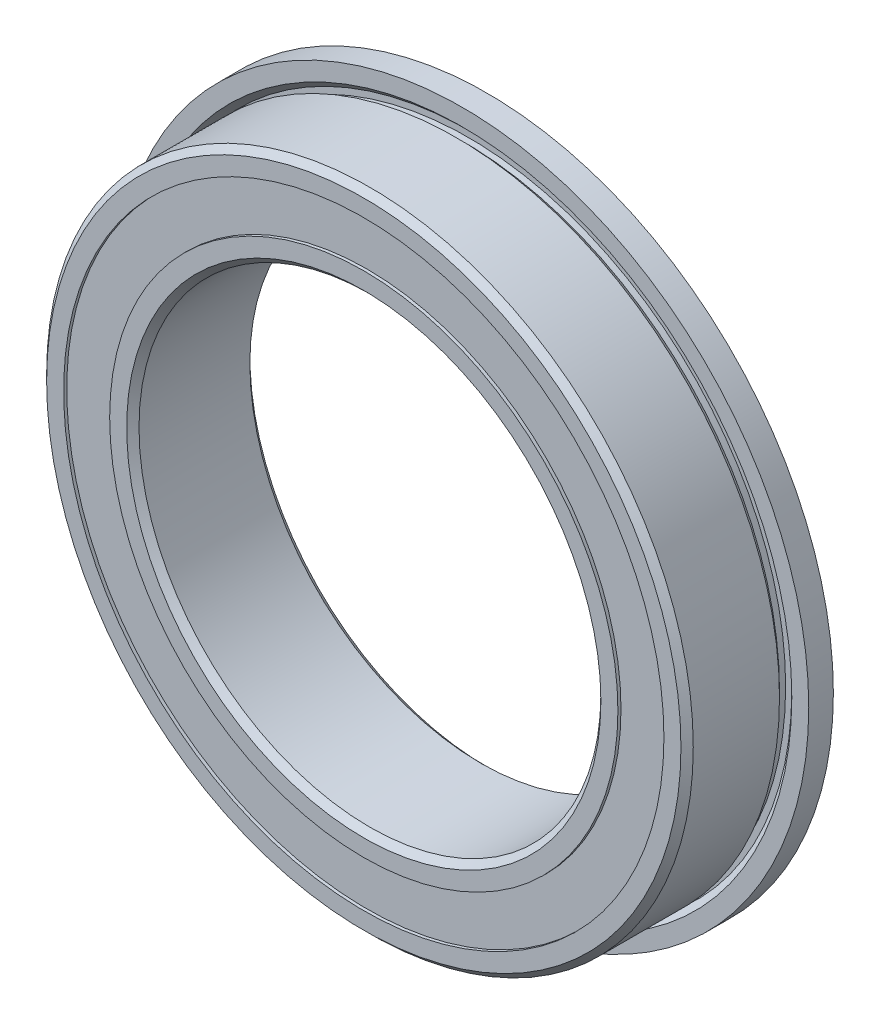
SolidWorks part; units mm, degrees
ref_plane "Front Plane" through (0, 0, 0) normal (0, 0, 1) x (1, 0, 0)
ref_plane "Top Plane" through (0, 0, 0) normal (0, 1, 0) x (1, 0, 0)
ref_plane "Right Plane" through (0, 0, 0) normal (1, 0, 0) x (0, 0, -1)
sketch "Sketch1" plane through (0, 0, 0) normal (0, 0, 1) x (1, 0, 0)
  circle A0 centre (0, 0) radius 7.5
  dimension "ID" = 15
sketch "Sketch2" plane through (0, 0, 0) normal (1, 0, 0) x (0, 0, -1)
  line L0 (-2, 0) -> (2, 0) construction
  line L1 (0, 10.5) -> (0, -10.5) construction
  line L2 (1.8, 10.5) -> (-1.8, 10.5) construction
  line L3 (-1.8, 10.5) -> (-2, 10.3)
  line L4 (-2, 10.3) -> (-2, 9.7473)
  line L5 (-2, 9.7473) -> (-0.8889, 9.7473)
  line L6 (2, 9.7473) -> (0.8889, 9.7473)
  line L7 (2, 10.3) -> (2, 9.7473)
  line L8 (1.8, 10.5) -> (2, 10.3) construction
  line L9 (0, 10.5) -> (0, 9) construction
  line L10 (0, 9) -> (0, 7.5) construction
  line L11 (1.2, 0) -> (1.2, 10.5) construction
  line L12 (2, 10.3) -> (2, 11.25)
  line L13 (2, 11.25) -> (1.2, 11.25)
  line L14 (1.2, 11.25) -> (1.2, 10.7)
  line L15 (1.2, 10.7) -> (1.4, 10.5)
  line L16 (1.4, 10.5) -> (1.4, 10.3)
  line L17 (1.4, 10.3) -> (1.2, 10.3)
  line L18 (1.2, 10.3) -> (1, 10.5)
  line L19 (-1.8, 10.5) -> (1, 10.5)
  line L20 (2, 11.25) -> (2, -11.25) construction
  line L21 (1.2, 10.5) -> (1.2, 10.7) construction
  line L22 (1.2, 10.5) -> (1, 10.5) construction
  line L23 (0, 7.5) -> (0, -7.5) construction
  arc A0 (-0.8889, 9.7473) -> (0.8889, 9.7473) centre (0, 9) cw
  point P14 (0, 7.5)
  point P15 (1.2, 0)
  point P25 (2, 0)
  point P29 (-1.8, -10.5)
  dimension "D1" = 45
  dimension "D2" = 0.2
  dimension "D3" = 1.7778
  dimension "D4" = 0.7473
  dimension "Flange Thickness" = 0.8
  dimension "Flange OD" = 22.5
  dimension "Width" = 4
  dimension "OD" = 21
sketch "Sketch7" plane through (0, 0, 0) normal (1, 0, 0) x (0, 0, -1)
  line L13 (2, 11.25) -> (1.2, 11.25)
  line L14 (1.2, 11.25) -> (1.2, 10.7)
  line L15 (1.2, 10.7) -> (1.4, 10.5)
  line L16 (1.4, 10.5) -> (1.4, 10.3)
  line L17 (1.4, 10.3) -> (1.2, 10.3)
  line L18 (1.2, 10.3) -> (1, 10.5)
  line L19 (1, 10.5) -> (-1.8, 10.5)
  line L20 (-1.8, 10.5) -> (-2, 10.3)
  line L21 (-2, 10.3) -> (-2, 9.7473)
  line L22 (-2, 9.7473) -> (-0.8889, 9.7473)
  line L23 (0.8889, 9.7473) -> (2, 9.7473)
  line L24 (2, 9.7473) -> (2, 10.3)
  line L25 (2, 10.3) -> (2, 11.25)
  line L26 (2, 11.25) -> (1.2, 11.25)
  line L27 (1.2, 11.25) -> (1.2, 10.7)
  line L28 (1.2, 10.7) -> (1.4, 10.5)
  line L29 (1.4, 10.5) -> (1.4, 10.3)
  line L30 (1.4, 10.3) -> (1.2, 10.3)
  line L31 (1.2, 10.3) -> (1, 10.5)
  line L32 (1, 10.5) -> (-1.8, 10.5)
  line L33 (-1.8, 10.5) -> (-2, 10.3)
  line L34 (-2, 10.3) -> (-2, 9.7473)
  line L35 (-2, 9.7473) -> (-0.8889, 9.7473)
  line L36 (0.8889, 9.7473) -> (2, 9.7473)
  line L37 (2, 9.7473) -> (2, 10.3)
  line L38 (2, 10.3) -> (2, 11.25)
  arc A1 (0.8889, 9.7473) -> (-0.8889, 9.7473) centre (0, 9) ccw
  arc A2 (0.8889, 9.7473) -> (-0.8889, 9.7473) centre (0, 9) ccw
  dimension "D1" = 0
revolve "Revolve7" add sketch "Sketch7" angle 360 about L0
sketch "Sketch3" plane through (0, 0, 0) normal (1, 0, 0) x (0, 0, -1)
  line L0 (-2, 8.2527) -> (-0.8889, 8.2527)
  line L1 (0, 10.5) -> (0, -10.5) construction
  line L2 (-2, 10.3) -> (-2, 9.7473) construction
  line L3 (-2, 8.2527) -> (-2, 7.7)
  line L4 (-1.8, 10.5) -> (-2, 10.3) construction
  line L5 (-2, 7.7) -> (-1.8, 7.5)
  line L6 (-1.8, 7.5) -> (1.8, 7.5)
  line L8 (1.8, 7.5) -> (2, 7.7)
  line L10 (2, 7.7) -> (2, 8.2527)
  line L11 (2, 8.2527) -> (0.8889, 8.2527)
  line L13 (1.8, 10.5) -> (2, 10.3) construction
  arc A0 (0.8889, 9.7473) -> (-0.8889, 9.7473) centre (0, 9) ccw construction
  arc A1 (0.8889, 8.2527) -> (-0.8889, 8.2527) centre (0, 9) cw
revolve "Revolve3" add sketch "Sketch3" angle 360 about L0
sketch "Sketch6" plane through (0, 0, 0) normal (1, 0, 0) x (0, 0, -1)
  line L1 (-0.1245, 9.3736) -> (0.1245, 9.3736)
  line L2 (-0.1245, 9.3736) -> (-0.1245, 8.6264)
  line L3 (-0.1245, 8.6264) -> (0.1245, 8.6264)
  line L4 (0.1245, 9.3736) -> (0.1245, 8.6264)
  line L5 (-0.1245, 9.3736) -> (0.1245, 8.6264) construction
  line L6 (-0.1245, 8.6264) -> (0.1245, 9.3736) construction
  point P4 (0, 9)
  dimension "D1" = 0.7473
  dimension "D2" = 0.2491
revolve "Revolve6" add sketch "Sketch6" angle 360 about L0
sketch "Sketch4" plane through (0, 0, 0) normal (1, 0, 0) x (0, 0, -1)
  line L0 (-1.1613, 9) -> (1.1613, 9)
  arc A2 (-1.1613, 9) -> (1.1613, 9) centre (0, 9) cw
  arc A3 (0.8889, 9.7473) -> (-0.8889, 9.7473) centre (0, 9) ccw construction
revolve "Revolve4" add sketch "Sketch4" angle 360 about L0
ref_axis "Axis1" through (0, 0, -2) along (0, 0, 1)
pattern_circular "CirPattern1" count 13 over 360 about axis through (0, 0, -2) along (0, 0, 1) of bodies 104
sketch "Sketch5" plane through (0, 0, 0) normal (1, 0, 0) x (0, 0, -1)
  line L0 (-2, 9.7473) -> (-0.8889, 9.7473) construction
  line L1 (-1.9, 9.7473) -> (-1.1613, 9.7473)
  line L2 (-1.9, 9.7473) -> (-1.9, 8.2527)
  line L3 (-1.9, 8.2527) -> (-1.1613, 8.2527)
  line L4 (-1.1613, 9.7473) -> (-1.1613, 8.2527)
  line L5 (-2, 8.2527) -> (-0.8889, 8.2527) construction
  line L6 (2, 9.7473) -> (0.8889, 9.7473) construction
  line L7 (1.9, 9.7473) -> (1.1613, 9.7473)
  line L8 (1.9, 9.7473) -> (1.9, 8.2527)
  line L9 (1.9, 8.2527) -> (1.1613, 8.2527)
  line L10 (1.1613, 9.7473) -> (1.1613, 8.2527)
  line L11 (2, 8.2527) -> (0.8889, 8.2527) construction
  line L12 (-1.8, 10.5) -> (-2, 10.3) construction
  point P18 (-1.9, 10.4)
revolve "Revolve5" add sketch "Sketch5" angle 360 about L0
equation "\"D2@Sketch2\" = \"Width@Sketch2\" * .05"
equation "\"D3@Sketch2\" = \"Width@Sketch2\" / 2.25"
equation "\"D4@Sketch2\" =  (  (  ( \"OD@Sketch2\" - \"Width@Sketch2\" )  / 2 )  / 3.25 )  / 3.5"
equation "\"D2@CirPattern1\" = 360/\"Balls@CirPattern1\""
equation "\"D1@Sketch6\" = \"D4@Sketch2\""
equation "\"D2@Sketch6\"=\"D1@Sketch6\"/3"
